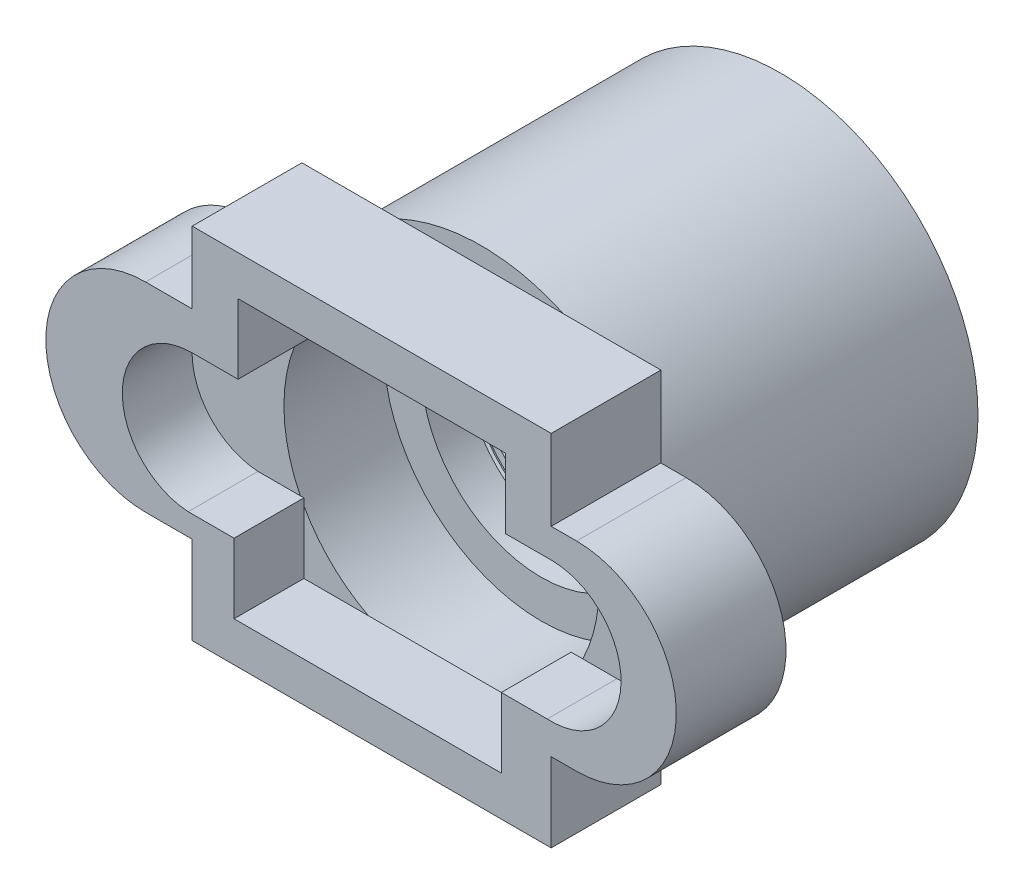
SolidWorks part; units mm, degrees
material "ABS"
ref_plane "Plan de face" through (0, 0, 0) normal (0, 0, 1) x (1, 0, 0)
ref_plane "Plan de dessus" through (0, 0, 0) normal (0, 1, 0) x (1, 0, 0)
ref_plane "Plan de droite" through (0, 0, 0) normal (1, 0, 0) x (0, 0, -1)
sketch "Esquisse2" plane through (0, 0, 0) normal (0, 0, 1) x (1, 0, 0)
  line L1 (-7, 7) -> (7, 7)
  line L3 (-7, -7) -> (7, -7)
  line L5 (-7, 7) -> (7, -7) construction
  line L6 (-7, -7) -> (7, 7) construction
  line L7 (-7, 3.4061) -> (-10.37, 3.4061)
  line L10 (-7, -2.5939) -> (-10.37, -2.5939)
  line L11 (7, 2.9638) -> (10.3794, 2.9638)
  line L13 (7, -3.0362) -> (10.3794, -3.0362)
  line L14 (0, 7) -> (0, 9) construction
  line L15 (0, -55) -> (0, 55) construction
  line L16 (0, 9) -> (9, 9)
  line L17 (9, 9) -> (9, 4.9638)
  line L18 (9, 4.9638) -> (10.2736, 4.9638)
  line L19 (10.2736, -5.0362) -> (9, -5.0362)
  line L20 (9, -5.0362) -> (9, -9)
  line L21 (9, -9) -> (-9, -9)
  line L22 (-9, -9) -> (-9, -4.5939)
  line L23 (-9, -4.5939) -> (-11.3374, -4.5939)
  line L24 (-11.3374, 5.4061) -> (-9, 5.4061)
  line L25 (-9, 5.4061) -> (-9, 9)
  line L26 (-9, 9) -> (0, 9)
  line L27 (-9, 9) -> (9, 9)
  line L28 (9, 4.9638) -> (10.2736, 4.9638)
  line L29 (10.2736, -5.0362) -> (9, -5.0362)
  line L30 (9, -9) -> (-9, -9)
  line L31 (-9, -4.5939) -> (-11.3374, -4.5939)
  line L32 (-11.3374, 5.4061) -> (-9, 5.4061)
  line L33 (-7, 7) -> (-7, 3.4061)
  line L34 (-10.37, -2.5939) -> (-7, -2.5939)
  line L35 (-7, -7) -> (7, -7)
  line L36 (7, -3.0362) -> (10.3794, -3.0362)
  line L37 (10.3794, 2.9638) -> (7, 2.9638)
  line L38 (7, 7) -> (-7, 7)
  line L39 (-7, -2.5939) -> (-7, -7)
  line L40 (7, 7) -> (7, 2.9638)
  line L41 (7, -3.0362) -> (7, -7)
  arc A0 (-10.37, 3.4061) -> (-10.37, -2.5939) centre (-10.37, 0.4061) ccw
  arc A1 (10.3794, -3.0362) -> (10.3794, 2.9638) centre (10.3794, -0.0362) ccw
  arc A2 (-11.3374, 5.4061) -> (-11.3374, -4.5939) centre (-11.3374, 0.4061) ccw
  arc A3 (10.2736, 4.9638) -> (10.2736, -5.0362) centre (10.2736, -0.0362) cw
  arc A4 (10.2736, 4.9638) -> (10.2736, -5.0362) centre (10.2736, -0.0362) cw
  arc A5 (-11.3374, 5.4061) -> (-11.3374, -4.5939) centre (-11.3374, 0.4061) ccw
  arc A6 (-10.37, 3.4061) -> (-10.37, -2.5939) centre (-10.37, 0.4061) ccw
  arc A7 (10.3794, 2.9638) -> (10.3794, -3.0362) centre (10.3794, -0.0362) cw
  point P0 (0, 0)
  dimension "D3" = 3
  dimension "D4" = 3
  dimension "D1" = 14
  dimension "D2" = 14
  dimension "D5" = 2
  dimension "D7" = 2
  dimension "D8" = 2
  dimension "D10" = 2
  dimension "D12" = 2
  dimension "D13" = 2
extrude "Boss.-Extru.2" add sketch "Esquisse2" along normal blind 5.5 contours A3 L19 L20 L21 L22 L23 A2 L24 L25 L26 L16 L17 L18
sketch "Esquisse7" plane through (0, 0, 5.5) normal (0, 0, 1) x (1, 0, 0)
  line L0 (9, -5.0362) -> (9, -9) construction
  line L2 (0, -10.89) -> (0, 10.89) construction
  line L3 (0, 7) -> (6.7, 7)
  line L4 (6.7, 7) -> (6.7, 3.5)
  line L5 (6.7, 3.5) -> (9, 3.5)
  line L6 (8.8, -3.5) -> (6.5, -3.5)
  line L7 (6.5, -3.5) -> (6.5, -7)
  line L8 (6.5, -7) -> (-6.9, -7)
  line L9 (-6.9, -7) -> (-6.9, -3.5)
  line L10 (-6.9, -3.5) -> (-9.2, -3.5)
  line L11 (0, 7) -> (-6.7, 7)
  line L12 (-6.7, 7) -> (-6.7, 3.5)
  line L13 (-6.7, 3.5) -> (-9, 3.5)
  line L15 (-9, 9) -> (9, 9) construction
  line L16 (9, -9) -> (-9, -9) construction
  arc A2 (-9, 3.5) -> (-9.2, -3.5) centre (-9, -0.0029) ccw
  arc A3 (9, 3.5) -> (8.8, -3.5) centre (9, -0.0029) cw
  point P23 (0, 0)
  point P24 (-10.2, 0)
  dimension "D9" = 2.3
  dimension "D1" = 6.7
  dimension "D2" = 6.7
  dimension "D3" = 3.5
  dimension "D4" = 3.5
  dimension "D5" = 3.5
  dimension "D6" = 3.5
  dimension "D7" = 2.3
  dimension "D8" = 2.3
  dimension "D10" = 2.3
  dimension "D11" = 13.4
  dimension "D12" = 2.5
  dimension "D13" = 5.5
  dimension "D14" = 5.5
  dimension "D15" = 5.5
extrude "Enlèv. mat.-Extru.1" cut sketch "Esquisse7" against normal blind 3.5
sketch "Esquisse8" plane through (0, 0, 2) normal (0, 0, 1) x (1, 0, 0)
  circle A0 centre (0, 0) radius 7.9
  dimension "D1" = 15.8
extrude "Enlèv. mat.-Extru.2" cut sketch "Esquisse8" against normal blind 3
sketch "Esquisse9" plane through (0, 0, 0) normal (0, 0, -1) x (-1, 0, 0)
  circle A0 centre (0, 0) radius 9.9
  circle A1 centre (0, 0) radius 7.9
  dimension "D1" = 19.8
extrude "Boss.-Extru.3" add sketch "Esquisse9" along normal blind 3
sketch "Esquisse10" plane through (0, 0, -3) normal (0, 0, -1) x (-1, 0, 0)
  circle A1 centre (0, 0) radius 6
  circle A3 centre (0, 0) radius 9.9
  dimension "D1" = 12
extrude "Boss.-Extru.6" add sketch "Esquisse10" along normal blind 12
thread "Filetage1" pitch 0.25 method extrude profile "Profil de filetage1" start angle 0, offset 0, length 10, pitch 0.5, diameter 12
ref_plane "Plan1" through (6, 0, -15) normal (0, -1, 0) x (1, 0, 0)
sketch "Profil de filetage1" plane through (6, 0, -15) normal (0, -1, 0) x (1, 0, 0)
  line L0 (0, 0) -> (0, 0.25) construction
  line L11 (0, 0) -> (0, 0.2187)
  line L12 (0, 0.2187) -> (-0.1353, 0.1406)
  line L13 (-0.1353, 0.1406) -> (-0.1353, 0.0781)
  line L15 (-0.1353, 0.0781) -> (0, 0)
  line L17 (-0.1353, 0.1094) -> (0, 0.1094) construction
  point P2 (0, 0)
  dimension "Pitch" = 0.25
  dimension "Profile_Angle" = 60
  dimension "Profile_Land" = 0.0625
  dimension "Profile_Height" = 0.1353
